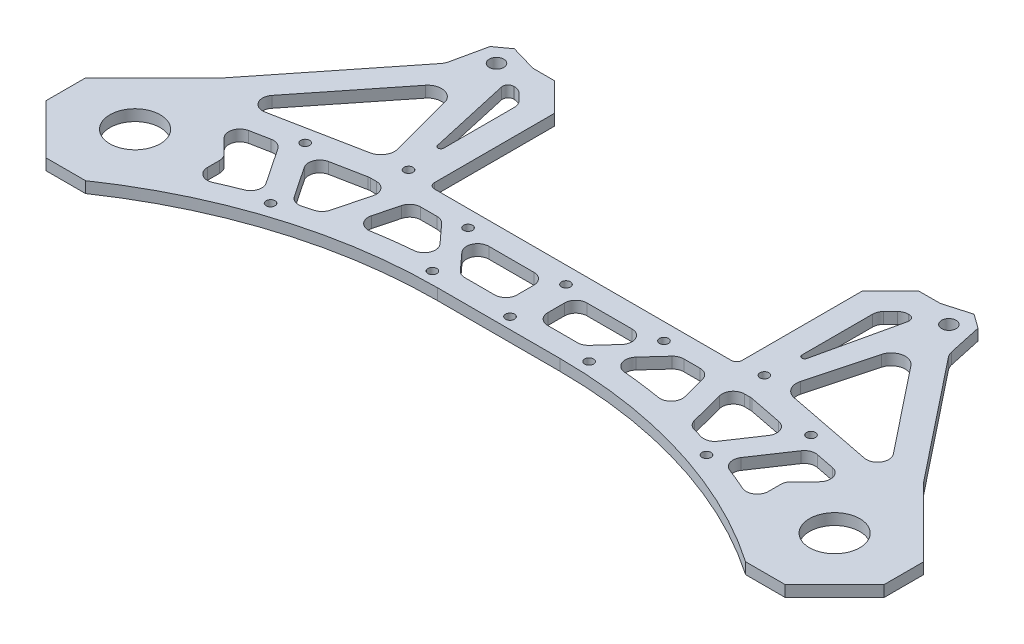
SolidWorks part; units mm, degrees
ref_plane "前视基准面" through (0, 0, 0) normal (0, 0, 1) x (1, 0, 0)
ref_plane "上视基准面" through (0, 0, 0) normal (0, 1, 0) x (1, 0, 0)
ref_plane "右视基准面" through (0, 0, 0) normal (1, 0, 0) x (0, 0, -1)
sketch "草图1" plane through (0, 0, 0) normal (0, 1, 0) x (1, 0, 0)
  line L0 (15.9099, 15.9099) -> (20, 20) construction
  line L1 (0, 31.8198) -> (-31.8198, 0)
  line L2 (-31.8198, 0) -> (0, -31.8198)
  line L3 (0, -31.8198) -> (31.8198, 0)
  line L4 (31.8198, 0) -> (0, 31.8198) construction
  line L5 (250, 31.8198) -> (218.1802, 0) construction
  line L6 (218.1802, 0) -> (250, -31.8198)
  line L7 (250, -31.8198) -> (281.8198, 0)
  line L8 (281.8198, 0) -> (250, 31.8198)
  line L9 (20, 20) -> (230, 20) construction
  line L10 (234.0901, 15.9099) -> (230, 20) construction
  line L11 (36.8198, 5) -> (213.1802, 5)
  line L12 (13.7868, 35) -> (230, 35)
  line L13 (31.8198, 0) -> (36.8198, 5)
  line L14 (244.6967, 26.5165) -> (236.2132, 35)
  line L15 (5.3033, 26.5165) -> (13.7868, 35)
  line L16 (218.1802, 0) -> (213.1802, 5)
  line L17 (244.6967, 26.5165) -> (240.6066, 30.6066) construction
  line L18 (5.3033, 26.5165) -> (9.3934, 30.6066) construction
  line L19 (20, 35) -> (230, 35) construction
  line L20 (230, 35) -> (236.2132, 35)
  line L22 (20, 5) -> (230, 5) construction
  line L24 (0, 31.8198) -> (5.3033, 26.5165)
  line L28 (244.6967, 26.5165) -> (250, 31.8198)
  circle A0 centre (0, 0) radius 9
  circle A1 centre (250, 0) radius 9
  circle A2 centre (0, 0) radius 22.5 construction
  circle A3 centre (250, 0) radius 22.5 construction
  point P23 (26.5165, 5.3033)
  point P24 (30.6066, 9.3934)
  point P29 (223.4835, 5.3033)
  point P30 (219.3934, 9.3934)
  dimension "D1" = 18
  dimension "D2" = 18
  dimension "D3" = 250
  dimension "D4" = 45
  dimension "D5" = 45
  dimension "D6" = 20
  dimension "D7" = 15
  dimension "D8" = 15
  dimension "D9" = 15
  dimension "D10" = 15
extrude "凸台-拉伸1" add sketch "草图1" along normal blind 4
fillet "圆角3" radius 50 2 edges at (236.2132, 2, -35) (13.7868, 2, -35)
chamfer "倒角1" distance 10 angle 45 4 edges at (281.8198, 2, 0) (250, 2, 31.8198) (0, 2, 31.8198) (-31.8198, 2, 0)
fillet "圆角4" radius 170 4 edges at (244.6967, 2, -26.5165) (5.3033, 2, -26.5165) (213.1802, 2, -5) (36.8198, 2, -5)
sketch "草图2" plane through (0, 4, 0) normal (0, 1, 0) x (1, 0, 0)
  line L0 (33.1669, 35) -> (44.1669, 35) construction
  line L1 (33.1669, 35) -> (216.8331, 35) construction
  line L2 (44.1669, 35) -> (44.1669, 85) construction
  line L3 (205.8331, 35) -> (205.8331, 85) construction
  line L4 (33.1669, 35) -> (70, 35)
  line L5 (125, 35) -> (125, -28.1037) construction
  line L6 (125, 35) -> (70, 35) construction
  line L7 (125, 35) -> (180, 35) construction
  line L8 (70, 35) -> (70, 89.938)
  line L9 (70, 89.938) -> (52.1738, 89.9808)
  line L10 (216.8331, 35) -> (205.8331, 35) construction
  line L11 (180, 89.938) -> (197.8262, 89.9808)
  line L12 (180, 35) -> (180, 89.938)
  line L13 (216.8331, 35) -> (180, 35)
  line L14 (41.2397, 89.0536) -> (37.1861, 86.1264)
  line L15 (41.2397, 89.0536) -> (45.2933, 91.9808)
  line L16 (212.8139, 86.1264) -> (215.0658, 75.8033)
  line L17 (208.7603, 89.0536) -> (212.8139, 86.1264)
  line L19 (45.2933, 91.9808) -> (52.1738, 89.9808)
  line L20 (37.1861, 86.1264) -> (34.9342, 75.8033)
  line L21 (208.7603, 89.0536) -> (204.7067, 91.9808)
  line L22 (204.7067, 91.9808) -> (197.8262, 89.9808)
  line L24 (34.9342, 75.8033) -> (0, 31.8198)
  line L25 (215.0658, 75.8033) -> (250, 31.8198)
  circle A0 centre (44.1669, 85) radius 2.6
  arc A2 (0, 31.8198) -> (24.6197, 34.264) centre (-4.4406, 201.7618) ccw construction
  arc A3 (33.1669, 35) -> (24.6197, 34.264) centre (33.1669, -15) ccw construction
  arc A4 (0, 31.8198) -> (24.6197, 34.264) centre (-4.4406, 201.7618) ccw
  arc A5 (33.1669, 35) -> (24.6197, 34.264) centre (33.1669, -15) ccw
  arc A6 (216.8331, 35) -> (225.3803, 34.264) centre (216.8331, -15) cw
  arc A7 (250, 31.8198) -> (225.3803, 34.264) centre (254.4406, 201.7618) cw
  circle A9 centre (205.8331, 85) radius 2.6
  dimension "D3" = 5.2
  dimension "D1" = 11
  dimension "D2" = 50
  dimension "D5" = 55
extrude "凸台-拉伸2" add sketch "草图2" against normal blind 4
chamfer "倒角2" distance 10 angle 45 2 edges at (180, 2, -89.938) (70, 2, -89.938) first distance on face at (180, 2, -62.469) first distance on face at (61.0869, 2, -89.9594)
fillet "圆角5" radius 2 2 edges at (180, 2, -35) (70, 2, -35)
fillet "圆角6" radius 5 3 edges at (34.9342, 2, -75.8033) (52.1738, 2, -89.9808) (197.8262, 2, -89.9808)
fillet "圆角7" radius 5 3 edges at (250, 2, -31.8198) (0, 2, -31.8198) (215.0658, 2, -75.8033)
sketch "草图3" plane through (0, 4, 0) normal (0, 1, 0) x (1, 0, 0)
  line L18 (6.1619, 25.2538) -> (-18.3848, 0.7071)
  line L19 (41.2594, 69.2964) -> (7.2252, 26.446)
  line L20 (45.9793, 84.2082) -> (43.9749, 75.0198)
  line L21 (125, 35) -> (125, 80.971) construction
  line L22 (41.2594, 69.2964) -> (7.2252, 26.446)
  line L23 (44.2875, 76.4528) -> (43.9749, 75.0198)
  line L24 (61, 37) -> (61, 79.914)
  line L25 (61, 37) -> (61, 76.1987)
  line L28 (44.2113, 76.3978) -> (52.3185, 82.2521)
  line L29 (44.2875, 76.4528) -> (50.5557, 80.9791)
  line L30 (63.6208, 73.5653) -> (53.6208, 83.6133)
  line L31 (61, 76.1987) -> (56.2505, 80.971)
  line L32 (52.858, 80.9791) -> (50.5557, 80.9791)
  line L33 (59.9784, 80.9621) -> (52.858, 80.9791)
  line L34 (56.2505, 80.971) -> (52.858, 80.9791)
  line L35 (61, 37) -> (7.2252, 26.446)
  line L36 (72, 35) -> (178, 35) construction
  line L37 (189, 37) -> (242.7748, 26.446)
  line L38 (193.7495, 80.971) -> (197.142, 80.9791)
  line L39 (197.142, 80.9791) -> (199.4443, 80.9791)
  line L40 (189, 76.1987) -> (193.7495, 80.971)
  line L41 (205.7125, 76.4528) -> (199.4443, 80.9791)
  line L42 (189, 37) -> (189, 76.1987)
  line L43 (205.7125, 76.4528) -> (206.0251, 75.0198)
  line L44 (208.7406, 69.2964) -> (242.7748, 26.446)
  arc A4 (208.7406, 69.2964) -> (206.0251, 75.0198) centre (219.7034, 78.0037) cw
  arc A6 (6.1619, 25.2538) -> (7.2252, 26.446) centre (-3.7376, 35.1533) ccw
  arc A7 (41.2594, 69.2964) -> (43.9749, 75.0198) centre (30.2966, 78.0037) ccw
  arc A9 (41.2594, 69.2964) -> (43.9749, 75.0198) centre (30.2966, 78.0037) ccw
  dimension "D1" = 9
  dimension "D2" = 9
  dimension "D3" = 12
  dimension "D4" = 9
  dimension "D5" = 9
extrude "切除-拉伸1" cut sketch "草图3" against normal blind 4
fillet "圆角8" radius 4 12 edges at (44.2875, 2, -76.4528) (50.5557, 2, -80.9791) (56.2505, 2, -80.971) (61, 2, -76.1987) (205.7125, 2, -76.4528) (199.4443, 2, -80.9791) (193.7495, 2, -80.971) (189, 2, -76.1987) (189, 2, -37) (61, 2, -37) (242.7748, 2, -26.446) (7.2252, 2, -26.446)
sketch "草图4" plane through (0, 4, 0) normal (0, 1, 0) x (1, 0, 0)
  line L0 (51.8489, 80.9791) -> (61, 40.2913)
  line L1 (49.5072, 80.222) -> (45.5277, 77.3483) construction
  line L2 (43.9643, 74.9717) -> (54.4495, 35.7144)
  line L3 (49.5072, 80.222) -> (45.5277, 77.3483)
  line L4 (125, 35) -> (125, 80.9791) construction
  line L5 (72, 35) -> (178, 35) construction
  line L6 (200.4928, 80.222) -> (204.4723, 77.3483)
  line L7 (206.0357, 74.9717) -> (195.5505, 35.7144)
  line L8 (198.1511, 80.9791) -> (189, 40.2913)
  line L9 (17.8826, 28.5377) -> (57.7704, 36.3661) construction
  line L10 (54.4495, 35.7144) -> (57.7704, 36.3661)
  line L11 (192.2296, 36.3661) -> (195.5505, 35.7144)
  arc A0 (51.8489, 80.9791) -> (49.5072, 80.222) centre (51.8489, 76.9791) ccw construction
  arc A1 (45.5277, 77.3483) -> (43.9643, 74.9717) centre (47.8694, 74.1054) ccw construction
  arc A2 (57.7704, 36.3661) -> (61, 40.2913) centre (57, 40.2913) ccw construction
  arc A3 (51.8489, 80.9791) -> (49.5072, 80.222) centre (51.8489, 76.9791) ccw
  arc A4 (45.5277, 77.3483) -> (43.9643, 74.9717) centre (47.8694, 74.1054) ccw
  arc A5 (57.7704, 36.3661) -> (61, 40.2913) centre (57, 40.2913) ccw
  arc A6 (192.2296, 36.3661) -> (189, 40.2913) centre (193, 40.2913) cw
  arc A7 (204.4723, 77.3483) -> (206.0357, 74.9717) centre (202.1306, 74.1054) cw
  arc A8 (198.1511, 80.9791) -> (200.4928, 80.222) centre (198.1511, 76.9791) cw
extrude "凸台-拉伸3" add sketch "草图4" against normal blind 4
fillet "圆角9" radius 1 2 edges at (61, 2, -40.2913) (189, 2, -40.2913)
fillet "圆角10" radius 2 2 edges at (198.1511, 2, -80.9791) (51.8489, 2, -80.9791)
fillet "圆角11" radius 5 2 edges at (195.5505, 2, -35.7144) (54.4495, 2, -35.7144)
fillet "圆角12" radius 5 2 edges at (206.0357, 2, -74.9717) (43.9643, 2, -74.9717)
sketch "草图5" plane through (0, 4, 0) normal (0, 1, 0) x (1, 0, 0)
  line L0 (-24.7487, -7.0711) -> (-7.0711, -24.7487) construction
  line L1 (-15.9099, -15.9099) -> (0, 0) construction
  line L2 (0, 0) -> (15.9099, 15.9099) construction
  line L3 (15.9099, 15.9099) -> (24.7487, 7.0711)
  line L4 (15.9099, 15.9099) -> (13.3445, 18.4753)
  line L7 (146.8582, 13) -> (103.1418, 13)
  line L8 (119.5088, 13) -> (103.1418, 13)
  line L9 (64.3898, 27) -> (56.7796, 27)
  line L10 (72, 27) -> (178, 27)
  line L11 (72, 27) -> (82.6808, 27)
  line L13 (50.9351, 25.8529) -> (56.7796, 27)
  line L14 (19.6159, 19.7061) -> (50.9351, 25.8529)
  line L15 (19.6159, 19.7061) -> (30.0217, 21.7484)
  line L16 (19.6159, 19.7061) -> (13.3445, 18.4753)
  line L17 (-24.7487, 0) -> (24.7487, 0) construction
  line L18 (-24.7487, 7.0711) -> (-24.7487, -7.0711) construction
  line L19 (0, 0) -> (0, 22.0131) construction
  line L20 (24.7487, -5.1922) -> (24.7487, 7.0711)
  line L21 (103.1418, 13) -> (90.3774, 27)
  line L23 (119.5088, 27) -> (119.5088, 13)
  line L24 (82.6808, 27) -> (95.5912, 12.8398)
  line L25 (72, 27) -> (67.4221, 9.3792)
  line L26 (64.3898, 27) -> (59.33, 7.524)
  line L27 (50.9351, 5.1719) -> (38.6751, 23.4468)
  line L28 (42.9302, 2.5069) -> (30.0217, 21.7484)
  line L29 (38.6751, 23.4468) -> (50.9351, 25.8529)
  line L30 (90.3774, 27) -> (119.5088, 27)
  line L31 (125, 35) -> (125, 70.9814) construction
  line L32 (72, 35) -> (178, 35) construction
  line L33 (250, 0) -> (250, 22.0131) construction
  line L34 (250, 0) -> (234.0901, 15.9099) construction
  line L35 (159.6226, 27) -> (130.4912, 27)
  line L36 (211.3249, 23.4468) -> (199.0649, 25.8529)
  line L37 (207.0698, 2.5069) -> (219.9783, 21.7484)
  line L38 (199.0649, 5.1719) -> (211.3249, 23.4468)
  line L39 (185.6102, 27) -> (190.67, 7.524)
  line L40 (178, 27) -> (182.5779, 9.3792)
  line L41 (167.3192, 27) -> (154.4088, 12.8398)
  line L42 (130.4912, 27) -> (130.4912, 13)
  line L43 (146.8582, 13) -> (159.6226, 27)
  line L44 (225.2513, -5.1922) -> (225.2513, 7.0711)
  line L45 (230.3841, 19.7061) -> (236.6555, 18.4753)
  line L46 (230.3841, 19.7061) -> (219.9783, 21.7484)
  line L47 (199.0649, 25.8529) -> (193.2204, 27)
  line L48 (178, 27) -> (167.3192, 27)
  line L49 (185.6102, 27) -> (193.2204, 27)
  line L50 (130.4912, 13) -> (146.8582, 13)
  line L51 (234.0901, 15.9099) -> (236.6555, 18.4753)
  line L52 (234.0901, 15.9099) -> (225.2513, 7.0711)
  arc A1 (33.1557, -1.3359) -> (24.7487, -5.1922) centre (103.1418, -165) ccw
  arc A2 (103.1418, 13) -> (2.5501, -18.1487) centre (103.1418, -165) ccw
  arc A3 (95.5912, 12.8398) -> (67.4221, 9.3792) centre (103.1418, -165) ccw
  arc A4 (42.9302, 2.5069) -> (33.1557, -1.3359) centre (103.1418, -165) ccw
  arc A5 (59.33, 7.524) -> (50.9351, 5.1719) centre (103.1418, -165) ccw
  arc A6 (190.67, 7.524) -> (199.0649, 5.1719) centre (146.8582, -165) cw
  arc A7 (207.0698, 2.5069) -> (216.8443, -1.3359) centre (146.8582, -165) cw
  arc A8 (154.4088, 12.8398) -> (182.5779, 9.3792) centre (146.8582, -165) cw
  arc A9 (216.8443, -1.3359) -> (225.2513, -5.1922) centre (146.8582, -165) cw
  dimension "D1" = 8
  dimension "D2" = 8
  dimension "D3" = 9
extrude "切除-拉伸2" cut sketch "草图5" against normal blind 4
fillet "圆角13" radius 4 36 edges at (30.0217, 2, -21.7484) (42.9302, 2, -2.5069) (24.7487, 2, 5.1922) (24.7487, 2, -7.0711) (13.3445, 2, -18.4753) (38.6751, 2, -23.4468) (50.9351, 2, -5.1719) (59.33, 2, -7.524) (56.7796, 2, -27) (64.3898, 2, -27) (72, 2, -27) (82.6808, 2, -27) (95.5912, 2, -12.8398) (67.4221, 2, -9.3792) (90.3774, 2, -27) (103.1418, 2, -13) (236.6555, 2, -18.4753) (225.2513, 2, -7.0711) (225.2513, 2, 5.1922) (207.0698, 2, -2.5069) (219.9783, 2, -21.7484) (193.2204, 2, -27) (211.3249, 2, -23.4468) (199.0649, 2, -5.1719) (190.67, 2, -7.524) (185.6102, 2, -27) (182.5779, 2, -9.3792) (154.4088, 2, -12.8398) (178, 2, -27) (167.3192, 2, -27) (159.6226, 2, -27) (146.8582, 2, -13) (119.5088, 2, -13) (130.4912, 2, -13) (130.4912, 2, -27) (119.5088, 2, -27)
sketch "草图6" plane through (0, 4, 0) normal (0, 1, 0) x (1, 0, 0)
  line L0 (37.1861, 86.1264) -> (37.8249, 89.0546)
  line L1 (45.2933, 91.9808) -> (42.8575, 92.6888)
  line L2 (37.1861, 86.1264) -> (45.2933, 91.9808)
  line L3 (125, 35) -> (125, 98.4303) construction
  line L4 (36.0153, 87.7479) -> (44.1224, 93.6022)
  line L5 (37.8249, 89.0546) -> (42.8575, 92.6888)
  line L6 (72, 35) -> (178, 35) construction
  line L7 (212.1751, 89.0546) -> (207.1425, 92.6888)
  line L8 (212.8139, 86.1264) -> (204.7067, 91.9808)
  line L9 (204.7067, 91.9808) -> (207.1425, 92.6888)
  line L10 (212.8139, 86.1264) -> (212.1751, 89.0546)
  dimension "D1" = 2
extrude "凸台-拉伸4" add sketch "草图6" against normal blind 4
sketch "草图7" plane through (0, 4, 0) normal (0, 1, 0) x (1, 0, 0)
  line L0 (125, 35) -> (125, 5) construction
  line L1 (72, 35) -> (178, 35) construction
  line L2 (103.1418, 5) -> (146.8582, 5) construction
  circle A0 centre (34.6096, 26.1728) radius 1.6
  circle A1 centre (47.1137, 1.3128) radius 1.6
  circle A2 centre (97, 9.2557) radius 1.6
  circle A3 centre (125, 29) radius 1.6
  circle A4 centre (125, 9) radius 1.6
  circle A5 centre (61.4166, 36.3097) radius 1.6
  circle A6 centre (188.5834, 36.3097) radius 1.6
  circle A7 centre (153, 9.2557) radius 1.6
  circle A8 centre (202.8863, 1.3128) radius 1.6
  circle A9 centre (215.3904, 26.1728) radius 1.6
  circle A10 centre (90, 29) radius 1.6
  circle A11 centre (160, 29) radius 1.6
  dimension "D1" = 35
  dimension "D2" = 28
  dimension "D3" = 20
  dimension "D4" = 6
extrude "切除-拉伸3" cut sketch "草图7" against normal blind 10
sketch "草图8" plane through (0, 4, 0) normal (0, 1, 0) x (1, 0, 0)
  line L0 (125, 35) -> (125, 29)
  line L3 (72, 35) -> (178, 35) construction
  line L4 (125, 29) -> (90, 29)
  line L5 (125, 29) -> (160, 29)
  line L6 (125, 29) -> (125, 9)
  line L7 (125, 9) -> (153, 9.2557)
  line L8 (125, 9) -> (97, 9.2557)
